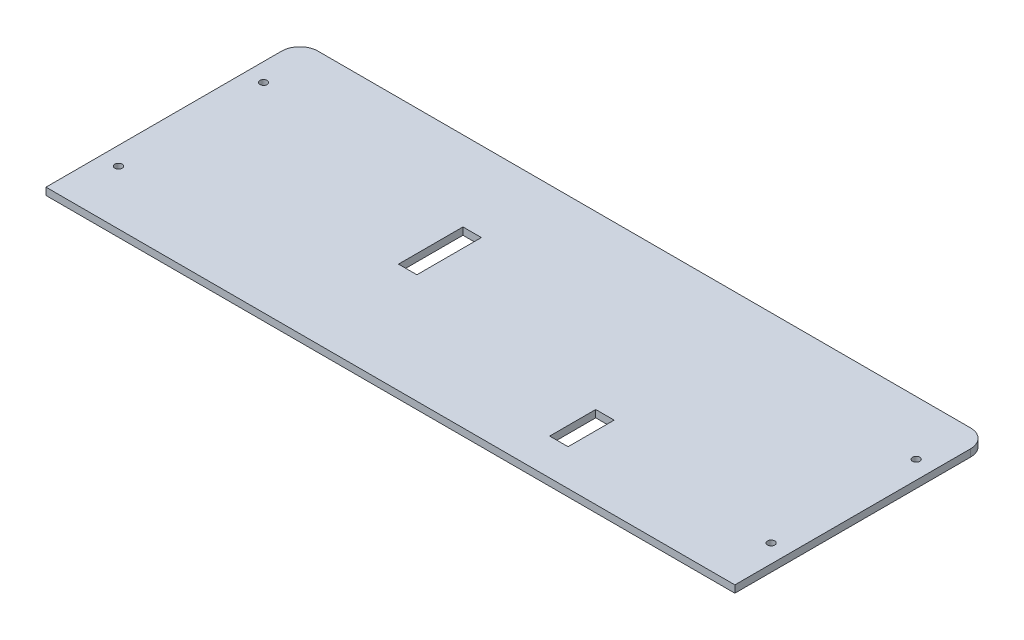
SolidWorks part; units mm, degrees
material "Калифорния"
ref_plane "Спереди" through (0, 0, 0) normal (0, 0, 1) x (1, 0, 0)
ref_plane "Сверху" through (0, 0, 0) normal (0, 1, 0) x (1, 0, 0)
ref_plane "Справа" through (0, 0, 0) normal (1, 0, 0) x (0, 0, -1)
sketch "Эскиз1" plane through (0, 0, 0) normal (0, 1, 0) x (1, 0, 0)
  line L0 (0, 56.6874) -> (0, -54.7718) construction
  line L1 (90, 35) -> (-90, 35)
  line L2 (95, 30) -> (95, -35)
  line L3 (95, -35) -> (-95, -35)
  line L4 (-95, 30) -> (-95, -35)
  line L5 (95, 35) -> (-95, -35) construction
  line L6 (95, -35) -> (-95, 35) construction
  line L8 (33.92, -25) -> (39, -25)
  line L9 (33.92, -25) -> (33.92, -12.3)
  line L10 (33.92, -12.3) -> (39, -12.3)
  line L11 (39, -25) -> (39, -12.3)
  line L12 (-28, -4.78) -> (-22.92, -4.78)
  line L13 (-28, -4.78) -> (-28, 13)
  line L14 (-28, 13) -> (-22.92, 13)
  line L15 (-22.92, -4.78) -> (-22.92, 13)
  arc A0 (90, 35) -> (95, 30) centre (90, 30) cw
  arc A1 (-90, 35) -> (-95, 30) centre (-90, 30) ccw
  circle A2 centre (-90, 20) radius 1
  circle A3 centre (-90, -20) radius 1
  circle A4 centre (90, -20) radius 1
  circle A5 centre (90, 20) radius 1
  point P0 (0, 0)
  dimension "D3" = 5
  dimension "D4" = 15
  dimension "D6" = 2
  dimension "D1" = 70
  dimension "D2" = 190
  dimension "D5" = 5
  dimension "D8" = 15
  dimension "D9" = 5.08
  dimension "D10" = 12.7
  dimension "D11" = 56
  dimension "D12" = 10
  dimension "D13" = 5.08
  dimension "D14" = 17.78
  dimension "D15" = 67
  dimension "D16" = 22
  dimension "D7" = 2
extrude "Сейвер" add sketch "Эскиз1" along normal blind 2
sketch "Эскиз2" plane through (0, 0, 0) normal (0, 1, 0) x (1, 0, 0)
  line L0 (-28, 13) -> (-28, -4.78) construction
  line L1 (90, 35) -> (-90, 35) construction
  line L2 (95, -35) -> (95, 30) construction
  circle A0 centre (30, 5) radius 5
  circle A1 centre (-43, 5) radius 5
  dimension "D1" = 10
  dimension "D2" = 10
  dimension "D3" = 15
  dimension "D4" = 30
  dimension "D5" = 30
  dimension "D6" = 65
extrude "Держатели экранов" add sketch "Эскиз2" against normal blind 14.5
fillet "Скругление1" radius 2 2 edges at (-43, 0, -10) (30, 0, -10) conic radius 10
